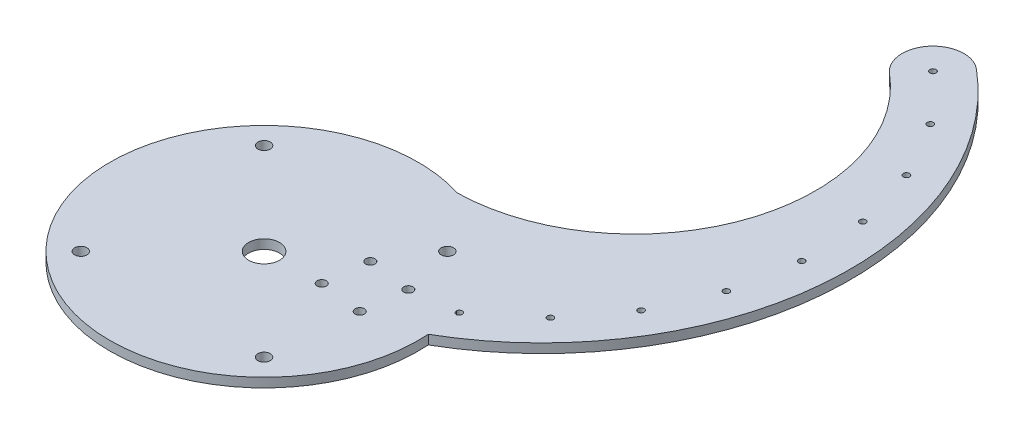
SolidWorks part; units mm, degrees
note: The reader was unsure of these and kept them because the rebuilt part matched: shared geometry of "Çizim4<3>".
ref_plane "Ön Düzlem" through (0, 0, 0) normal (0, 0, 1) x (1, 0, 0)
ref_plane "Üst Düzlem" through (0, 0, 0) normal (0, 1, 0) x (1, 0, 0)
ref_plane "Sağ Düzlem" through (0, 0, 0) normal (1, 0, 0) x (0, 0, -1)
sketch "Çizim1" plane through (0, 0, 0) normal (0, 1, 0) x (1, 0, 0)
  circle A0 centre (0, 0) radius 50
  dimension "D1" = 100
extrude "top cover" add sketch "Çizim1" along normal blind 3
sketch "Çizim2" plane through (0, 3, 0) normal (0, 1, 0) x (1, 0, 0)
  circle A0 centre (0, 0) radius 42 construction
  circle A1 centre (-29.6985, 29.6985) radius 2
  circle A2 centre (29.6985, 29.6985) radius 2
  circle A3 centre (29.6985, -29.6985) radius 2
  circle A4 centre (-29.6985, -29.6985) radius 2
  circle A5 centre (0, 0) radius 50 construction
  point P14 (0, 0)
  dimension "D1" = 4
  dimension "D3" = 8
  dimension "D2" = 4
extrude "spacer delikler" cut sketch "Çizim2" against normal through all
sketch "Çizim3" plane through (0, 3, 0) normal (0, 1, 0) x (1, 0, 0)
  line L1 (57.8509, 158.944) -> (0, 90) construction
  line L3 (0, 90) -> (0, 0) construction
  circle A2 centre (0, 0) radius 50 construction
  circle A8 centre (0, 90) radius 100 construction
  circle A9 centre (0, 0) radius 10
  arc A10 (0, 0) -> (57.8509, 158.944) centre (0, 90) ccw
  circle A11 centre (72.2462, 143.6702) radius 1
  circle A12 centre (82.7124, 125.4776) radius 1
  arc A13 (51.423, 151.2836) -> (15, 47.697) centre (13.7155, 106.3454) cw
  arc A14 (51.423, 151.2836) -> (64.2788, 166.6044) centre (57.8509, 158.944) cw
  arc A15 (64.2788, 166.6044) -> (0, -10) centre (0, 90) cw
  circle A16 centre (57.8509, 158.944) radius 1
  circle A17 centre (88.6804, 105.3556) radius 1
  circle A18 centre (89.8255, 84.3985) radius 1
  circle A19 centre (86.0856, 63.746) radius 1
  circle A20 centre (77.6639, 44.5213) radius 1
  circle A21 centre (65.0186, 27.7699) radius 1
  circle A22 centre (48.8373, 14.4029) radius 1
  circle A23 centre (30, 5.1472) radius 1
  circle A24 centre (0, 90) radius 10
  point P5 (51.423, 151.2836)
  point P6 (15, 47.697)
  point P37 (0, 90)
  dimension "D1" = 20
  dimension "D2" = 200
  dimension "D4" = 15
  dimension "D7" = 2
  dimension "D3" = 140
  dimension "D5" = 10
  dimension "D8" = 15
  dimension "D6" = 10
sketch "Çizim4" plane through (0, 3, 0) normal (0, 1, 0) x (1, 0, 0)
  line L1 (20.0417, 14.3924) -> (34.0793, 12.6757) construction
  circle A0 centre (0, 0) radius 5
  circle A2 centre (26.2021, 6.5153) radius 10 construction
  circle A3 centre (34.0793, 12.6757) radius 1.5
  circle A4 centre (32.3625, -1.3619) radius 1.5
  circle A5 centre (18.325, 0.3549) radius 1.5
  circle A6 centre (20.0417, 14.3924) radius 1.5
  circle A7 centre (26.2021, 6.5153) radius 5
  circle A9 centre (26.2021, 6.5153) radius 12.5 construction
  arc A10 (0, -10) -> (64.2788, 166.6044) centre (0, 90) ccw construction
  point P22 (26.2021, 6.5153)
  dimension "D1" = 10
  dimension "D2" = 20
  dimension "D3" = 3
  dimension "D6" = 25
  dimension "D5" = 27
  dimension "D4" = 4
extrude "Kes-Ekstrüzyon3" cut sketch "Çizim4" against normal through all contours A0
extrude "Kes-Ekstrüzyon4" cut sketch "Çizim4<3>" against normal through all
sketch "Çizim4<3>" plane through (0, 3, 0) normal (0, 1, 0) x (1, 0, 0) same geometry as "Çizim4"
extrude "kanca delikleri" add sketch "Çizim3" against normal blind 3
